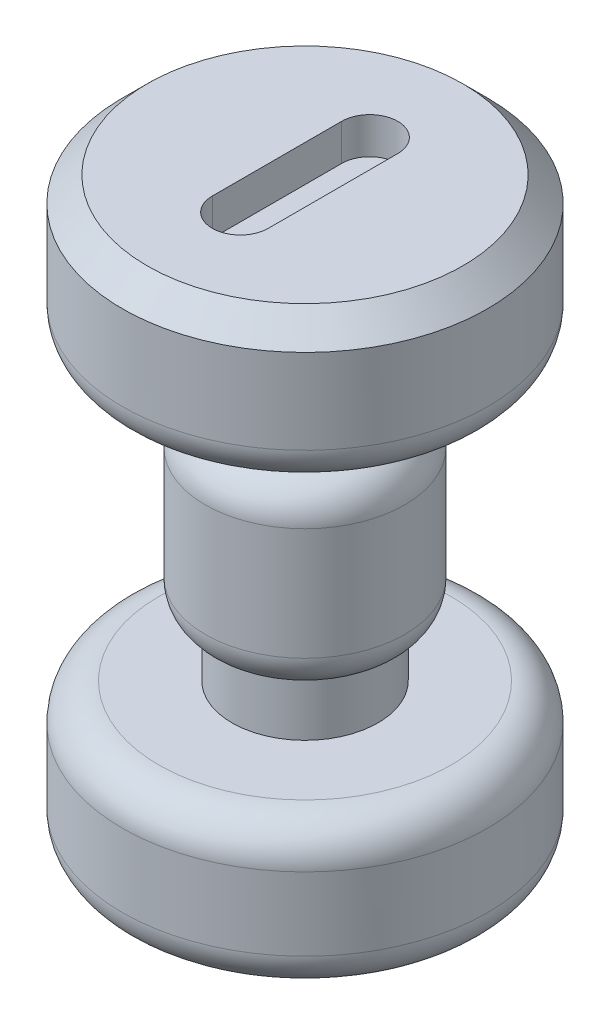
SolidWorks part; units mm, degrees
ref_plane "前视基准面" through (0, 0, 0) normal (0, 0, 1) x (1, 0, 0)
ref_plane "上视基准面" through (0, 0, 0) normal (0, 1, 0) x (1, 0, 0)
ref_plane "右视基准面" through (0, 0, 0) normal (1, 0, 0) x (0, 0, -1)
sketch "草图2" plane through (0, 0, 0) normal (0, 0, 1) x (1, 0, 0)
  line L0 (0, 0) -> (-25, 0)
  line L1 (-25, 0) -> (-25, 20)
  line L2 (-25, 20) -> (-10, 20)
  line L3 (-10, 20) -> (-10, 60)
  line L4 (-10, 60) -> (-25, 60)
  line L5 (-25, 60) -> (-25, 80)
  line L6 (-25, 80) -> (0, 80)
  line L7 (0, 80) -> (0, 0)
  point P3 (0, 74.5358)
  dimension "D1" = 25
  dimension "D2" = 20
  dimension "D3" = 10
  dimension "D4" = 80
revolve "旋转1" add sketch "草图2" angle 360 about L7
ref_plane "基准面1" through (0, 40, 0) normal (0, 1, 0) x (1, 0, 0)
sketch "草图3" plane through (0, 40, 0) normal (0, 1, 0) x (1, 0, 0)
  circle A0 centre (0, 0) radius 13.6619
extrude "凸台-拉伸1" add sketch "草图3" against normal mid plane 25
sketch "草图4" plane through (0, 80, 0) normal (0, 1, 0) x (1, 0, 0)
  line L0 (0, -8.8652) -> (0, 8.8652) construction
  line L1 (-3.8342, -8.8652) -> (-3.8342, 8.8652)
  line L2 (3.8342, -8.8652) -> (3.8342, 8.8652)
  arc A0 (-3.8342, -8.8652) -> (3.8342, -8.8652) centre (0, -8.8652) ccw
  arc A1 (3.8342, 8.8652) -> (-3.8342, 8.8652) centre (0, 8.8652) ccw
  point P2 (0, 0)
extrude "切除-拉伸1" cut sketch "草图4" against normal blind 5
sketch "草图5" plane through (0, 0, 0) normal (1, 0, 0) x (0, 0, -1)
  line L0 (-25, 80) -> (-25, 76.608)
  line L1 (-25, 80) -> (-25, 60) construction
  line L2 (-25, 76.608) -> (-21.608, 80)
  line L3 (25, 80) -> (-25, 80) construction
  line L4 (-21.608, 80) -> (-25, 80)
  line L5 (0, 0) -> (0, 87.0972) construction
revolve "切除-旋转1" cut sketch "草图5" angle 360 about L5
fillet "圆角1" radius 5 5 edges at (-25, 0, 0) (-13.6619, 27.5, 0) (-13.6619, 52.5, 0) (-25, 60, 0) (-25, 20, 0)
